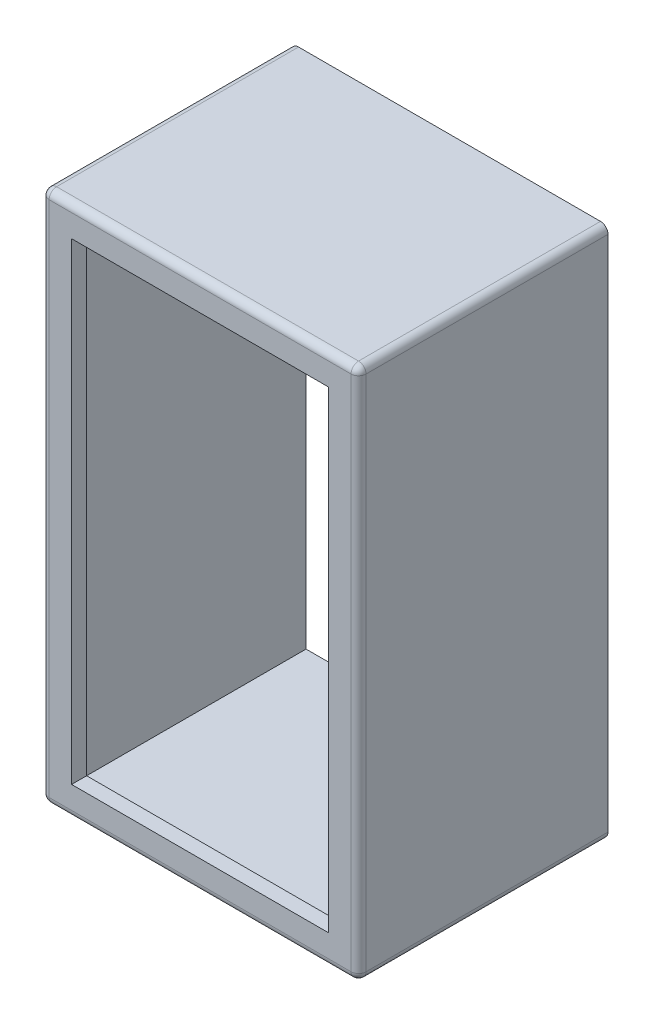
SolidWorks part; units mm, degrees
material "Nylon 101"
ref_plane "Front Plane" through (0, 0, 0) normal (0, 0, 1) x (1, 0, 0)
ref_plane "Top Plane" through (0, 0, 0) normal (0, 1, 0) x (1, 0, 0)
ref_plane "Right Plane" through (0, 0, 0) normal (1, 0, 0) x (0, 0, -1)
sketch "Sketch1" plane through (0, 0, 0) normal (0, 0, 1) x (1, 0, 0)
  line L1 (8.9229, 51.2767) -> (20.4164, 51.2767) construction
  line L2 (8.9229, 51.2767) -> (8.9229, 32.4807) construction
  line L3 (8.9229, 32.4807) -> (20.4164, 32.4807) construction
  line L4 (20.4164, 51.2767) -> (20.4164, 32.4807) construction
  line L7 (9.3039, 50.8957) -> (20.0354, 50.8957)
  line L8 (20.0354, 50.8957) -> (20.0354, 32.8617)
  line L9 (9.3039, 32.8617) -> (20.0354, 32.8617)
  line L10 (9.3039, 50.8957) -> (9.3039, 32.8617)
  point P4 (12.7998, 41.6606)
  dimension "D1" = 0.381
extrude "Boss-Extrude1" add sketch "Sketch1" along normal blind 7.9375
shell "Shell1" thickness 0.508 removed face at (14.6696, 41.8787, 0) removed face at (14.6696, 41.8787, 7.9375)
sketch "Sketch2" plane through (0, 0, 7.9375) normal (0, 0, 1) x (1, 0, 0)
  line L5 (9.8119, 50.3877) -> (9.8119, 33.3697)
  line L6 (19.5274, 50.3877) -> (9.8119, 50.3877)
  line L7 (19.5274, 33.3697) -> (19.5274, 50.3877)
  line L8 (9.8119, 33.3697) -> (19.5274, 33.3697)
  line L9 (9.8119, 50.3877) -> (9.8119, 33.3697)
  line L10 (19.5274, 50.3877) -> (9.8119, 50.3877)
  line L11 (19.5274, 33.3697) -> (19.5274, 50.3877)
  line L12 (9.8119, 33.3697) -> (19.5274, 33.3697)
  dimension "D1" = 0
extrude "Extrude-Thin1" add sketch "Sketch2" along normal blind 0.508 thin thin type mid plane wall 1.016
fillet "Fillet2" radius 0.254 8 edges at (9.3039, 50.8957, 4.2227) (20.0354, 50.8957, 4.2227) (20.0354, 32.8617, 4.2227) (9.3039, 32.8617, 4.2227) (14.6696, 50.8957, 8.4455) (20.0354, 41.8787, 8.4455) (14.6696, 32.8617, 8.4455) (9.3039, 41.8787, 8.4455)
